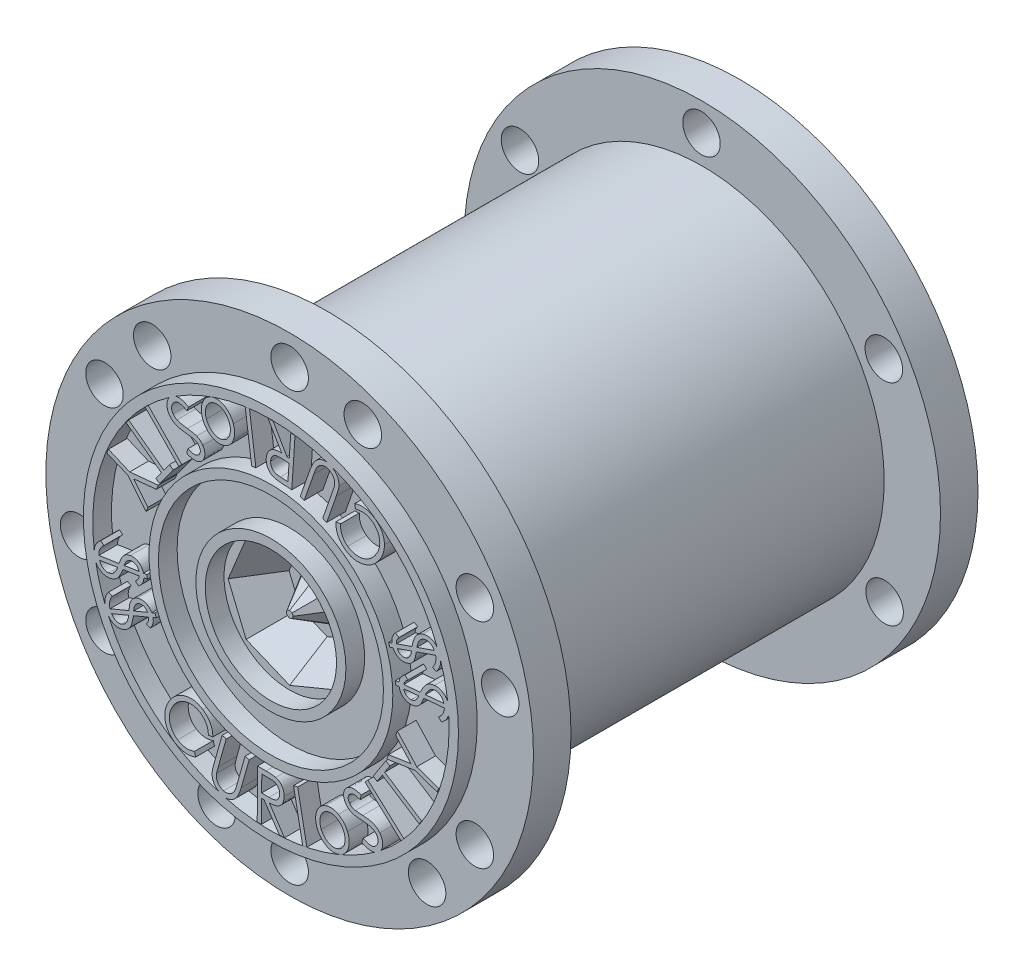
SolidWorks part; units mm, degrees
ref_plane "Front Plane" through (0, 0, 0) normal (0, 0, 1) x (1, 0, 0)
ref_plane "Top Plane" through (0, 0, 0) normal (0, 1, 0) x (1, 0, 0)
ref_plane "Right Plane" through (0, 0, 0) normal (1, 0, 0) x (0, 0, -1)
sketch "Sketch1" plane through (0, 0, 0) normal (0, 0, 1) x (1, 0, 0)
  circle A0 centre (0, 0) radius 6.5
  dimension "D1" = 13
extrude "Boss-Extrude1" add sketch "Sketch1" along normal blind 1
sketch "Sketch2" plane through (0, 0, 1) normal (0, 0, 1) x (1, 0, 0)
  circle A0 centre (0, 0) radius 2
  circle A1 centre (0, 0) radius 1.75
  dimension "D1" = 3.5
  dimension "D2" = 4
extrude "Boss-Extrude2" add sketch "Sketch2" along normal blind 0.5
sketch "Sketch3" plane through (0, 0, 1) normal (0, 0, 1) x (1, 0, 0)
  circle A0 centre (0, 0) radius 3
  circle A1 centre (0, 0) radius 3.25
  dimension "D1" = 6
  dimension "D2" = 6.5
extrude "Boss-Extrude3" add sketch "Sketch3" along normal blind 0.5
sketch "Sketch5" plane through (0, 0, 1) normal (0, 0, 1) x (1, 0, 0)
  circle A0 centre (0, 0) radius 5
  circle A1 centre (0, 0) radius 4.75
  dimension "D1" = 10
  dimension "D2" = 9.5
extrude "Boss-Extrude5" add sketch "Sketch5" along normal blind 0.5
sketch "Sketch7" plane through (0, 0, 1) normal (0, 0, 1) x (1, 0, 0)
  text T0 "$$  CURIoSITY  $$  CURIoSITY\r\n" font "Century Gothic" height 1.3
extrude "Boss-Extrude6" add sketch "Sketch7" along normal blind 0.5
sketch "Sketch8" plane through (0, 0, 0) normal (0, 0, -1) x (-1, 0, 0)
  circle A0 centre (0, 0) radius 4.85
  dimension "D1" = 9.7
extrude "Boss-Extrude7" add sketch "Sketch8" along normal blind 10
sketch "Sketch9" plane through (0, 0, -10) normal (0, 0, -1) x (-1, 0, 0)
  circle A0 centre (0, 0) radius 6.35
extrude "Boss-Extrude8" add sketch "Sketch9" along normal blind 1
sketch "Sketch11" plane through (0, 0, 1) normal (0, 0, 1) x (1, 0, 0)
  line L0 (1.6404, 0) -> (1.1599, 1.1599)
  line L1 (0, 1.6404) -> (-1.1599, 1.1599)
  line L2 (-1.1599, 1.1599) -> (-1.6404, 0)
  line L3 (-1.6404, 0) -> (-1.1599, -1.1599)
  line L4 (-1.1599, -1.1599) -> (0, -1.6404)
  line L5 (0, -1.6404) -> (1.1599, -1.1599)
  line L6 (1.1599, -1.1599) -> (1.6404, 0)
  line L7 (1.1599, 1.1599) -> (0, 1.6404)
  circle A0 centre (0, 0) radius 1.5155 construction
extrude "Cut-Extrude3" cut sketch "Sketch11" against normal blind 1 draft 30
sketch "Sketch12" plane through (0, 0, 0) normal (0, 0, 1) x (1, 0, 0)
  line L1 (0, 0.7159) -> (-0.5062, 0.5062)
  line L2 (-0.5062, 0.5062) -> (-0.7159, 0)
  line L3 (-0.7159, 0) -> (-0.5062, -0.5062)
  line L4 (-0.5062, -0.5062) -> (0, -0.7159)
  line L5 (0, -0.7159) -> (0.5062, -0.5062)
  line L6 (0.5062, -0.5062) -> (0.7159, 0)
  line L7 (0.7159, 0) -> (0.5062, 0.5062)
  line L8 (0.5062, 0.5062) -> (0, 0.7159)
  circle A0 centre (0, 0) radius 0.6614 construction
extrude "Boss-Extrude9" add sketch "Sketch12" along normal blind 1 draft 30
sketch "Sketch13" plane through (0, 0, 1) normal (0, 0, 1) x (1, 0, 0)
  circle A0 centre (0, 5.7) radius 0.5
  circle A1 centre (0, 0) radius 6.5 construction
  circle A2 centre (1.9495, 5.3562) radius 0.5
  circle A3 centre (4.9363, 2.85) radius 0.5
  circle A4 centre (5.6134, 0.9898) radius 0.5
  circle A5 centre (4.9363, -2.85) radius 0.5
  circle A6 centre (3.6639, -4.3665) radius 0.5
  circle A7 centre (0, -5.7) radius 0.5
  circle A8 centre (-1.9495, -5.3562) radius 0.5
  circle A9 centre (-4.9363, -2.85) radius 0.5
  circle A10 centre (-5.6134, -0.9898) radius 0.5
  circle A11 centre (-4.9363, 2.85) radius 0.5
  circle A12 centre (-3.6639, 4.3665) radius 0.5
  dimension "D1" = 1
  dimension "D2" = 5.7
  dimension "D3" = 2
  dimension "D4" = 6
extrude "Cut-Extrude4" cut sketch "Sketch13" against normal blind 1
sketch "Sketch14" plane through (0, 0, -11) normal (0, 0, -1) x (-1, 0, 0)
  line L1 (0, 2.3094) -> (-2, 1.1547)
  line L2 (-2, 1.1547) -> (-2, -1.1547)
  line L3 (-2, -1.1547) -> (0, -2.3094)
  line L4 (0, -2.3094) -> (2, -1.1547)
  line L5 (2, -1.1547) -> (2, 1.1547)
  line L6 (2, 1.1547) -> (0, 2.3094)
  circle A0 centre (0, 0) radius 2 construction
  dimension "D1" = 4
extrude "Cut-Extrude5" cut sketch "Sketch14" against normal blind 2
sketch "Sketch15" plane through (0, 0, -11) normal (0, 0, -1) x (-1, 0, 0)
  circle A0 centre (0.0206, 5.6) radius 0.5
  circle A1 centre (4.8601, 2.7821) radius 0.5
  circle A2 centre (4.8394, -2.8179) radius 0.5
  circle A3 centre (-0.0206, -5.6) radius 0.5
  circle A4 centre (-4.8601, -2.7821) radius 0.5
  circle A5 centre (-4.8394, 2.8179) radius 0.5
  dimension "D1" = 1
  dimension "D2" = 5.6
  dimension "D3" = 6
extrude "Cut-Extrude6" cut sketch "Sketch15" against normal blind 2
scale "Scale2" scale about centroid uniform scaling yes scale factor 20
sketch "Sketch16" plane through (0, 0, 111.2649) normal (0, 0, 1) x (1, 0, 0)
  circle A1 centre (0, 0) radius 99.9946
  circle A2 centre (0, 0) radius 129.9946
extrude "Cut-Extrude7" cut sketch "Sketch16" along normal blind 254
